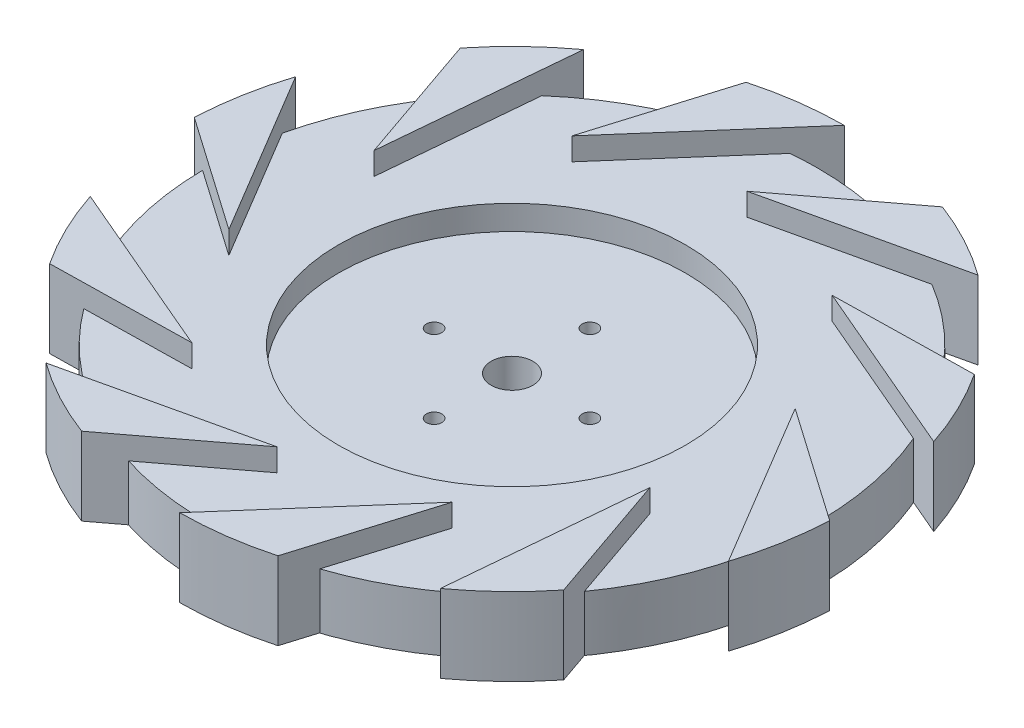
SolidWorks part; units mm, degrees
ref_plane "Front Plane" through (0, 0, 0) normal (0, 0, 1) x (1, 0, 0)
ref_plane "Top Plane" through (0, 0, 0) normal (0, 1, 0) x (1, 0, 0)
ref_plane "Right Plane" through (0, 0, 0) normal (1, 0, 0) x (0, 0, -1)
sketch "Sketch3" plane through (0, 0, 0) normal (0, 0, 1) x (1, 0, 0)
  line L0 (0, 0) -> (0, 40.1505) construction
  line L1 (-69.85, 16.0734) -> (-39.624, 16.0734)
  line L2 (-39.624, 16.0734) -> (-39.624, 10.4854)
  line L3 (-39.624, 10.4854) -> (0, 10.4854)
  line L4 (0, 10.4854) -> (0, 3.3734)
  line L5 (0, 3.3734) -> (-69.85, 3.3734)
  line L6 (-69.85, 3.3734) -> (-69.85, 16.0734)
  dimension "D1" = 12.7
  dimension "D2" = 69.85
  dimension "D3" = 39.624
  dimension "D4" = 5.588
revolve "Body" add sketch "Sketch3" angle 360 about L0
sketch "Sketch4" plane through (0, 0, 0) normal (0, 1, 0) x (1, 0, 0)
  line L0 (1.5533, 52.0769) -> (26.9502, 71.275)
  line L2 (44.4909, 61.8627) -> (1.5533, 52.0769)
  circle A1 centre (0, 0) radius 76.2 construction
  arc A3 (26.9502, 71.275) -> (44.4909, 61.8627) centre (0, 0) cw
extrude "Guide Vanes" add sketch "Sketch4" along direction (0, 1, 0) on the side of the normal blind 15.24 and the other way blind 2.54 from offset 5.969
pattern_circular "CirPattern4" count 10 over 360 about axis through (0, 16.0734, 0) along (0, -1, 0) of "Guide Vanes"
sketch "Sketch5" plane through (0, 3.3734, 0) normal (0, -1, 0) x (1, 0, 0)
  circle A0 centre (0, 0) radius 60.325
  dimension "D1" = 120.65
sketch "Sketch6" plane through (0, 0, 0) normal (0, 1, 0) x (1, 0, 0)
  circle A0 centre (0, 17.78) radius 1.7526
  dimension "D1" = 3.5052
  dimension "D2" = 17.78
extrude "Cut-Extrude1" cut sketch "Sketch6" along normal blind 13.97
pattern_circular "CirPattern5" count 4 over 360 about axis through (0, 16.0734, 0) along (0, -1, 0) of "Cut-Extrude1"
sketch "Sketch9" plane through (0, 10.4854, 0) normal (0, 1, 0) x (1, 0, 0)
  circle A0 centre (0, 0) radius 4.7625
  dimension "D1" = 9.525
extrude "Cut-Extrude2" cut sketch "Sketch9" against normal blind 7.62
sketch "Sketch8" plane through (0, 0, 0) normal (0, 1, 0) x (1, 0, 0)
  circle A0 centre (0, 0) radius 76.2 construction
